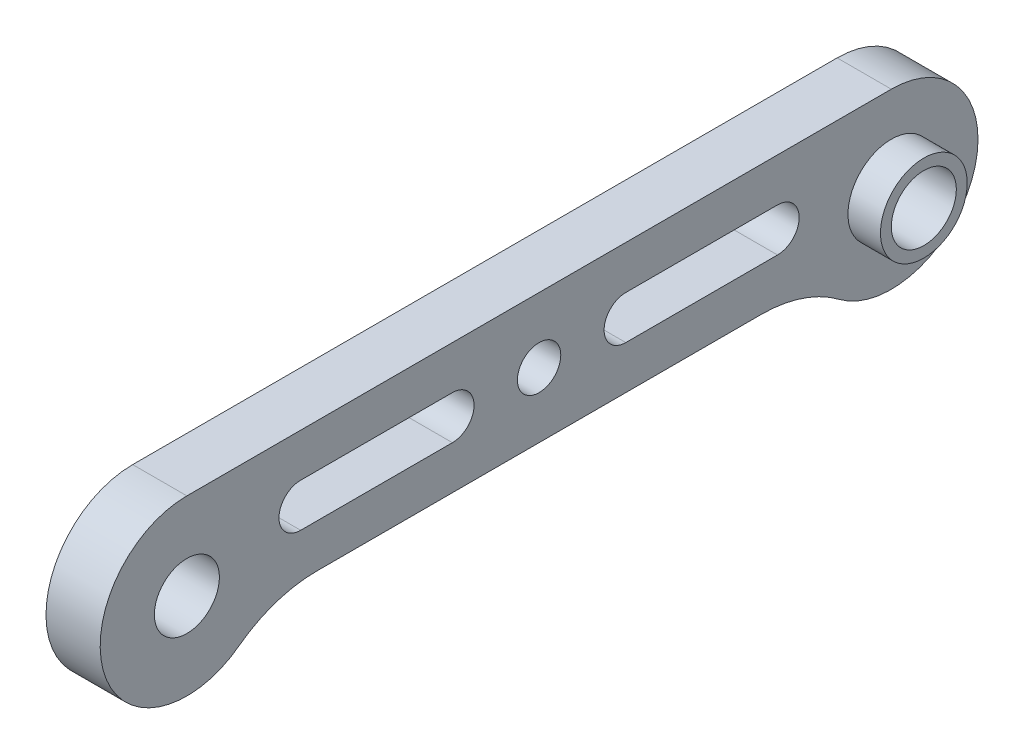
SolidWorks part; units mm, degrees
material "ABS"
ref_plane "前视基准面" through (0, 0, 0) normal (0, 0, 1) x (1, 0, 0)
ref_plane "上视基准面" through (0, 0, 0) normal (0, 1, 0) x (1, 0, 0)
ref_plane "右视基准面" through (0, 0, 0) normal (1, 0, 0) x (0, 0, -1)
other "Configuration Table"
sketch "草图1" plane through (0, 0, 0) normal (1, 0, 0) x (0, 0, -1)
  line L0 (0, 0) -> (-65, 0) construction
  line L1 (-65, 8) -> (0, 8)
  line L2 (-6.9282, -4) -> (-58.0718, -4)
  line L3 (0, -4) -> (-65, -4) construction
  circle A0 centre (-65, 0) radius 3
  circle A2 centre (-65, 0) radius 5 construction
  circle A3 centre (0, 0) radius 5 construction
  arc A4 (-65, 8) -> (-58.0718, -4) centre (-65, 0) ccw
  arc A5 (-6.9282, -4) -> (0, 8) centre (0, 0) ccw
  circle A6 centre (0, 0) radius 3
  dimension "D2" = 6
  dimension "D3" = 10
  dimension "D4" = 16
  dimension "D5" = 16
  dimension "D7" = 6
  dimension "D1" = 65
  dimension "D6" = 4
extrude "凸台-拉伸1" add sketch "草图1" along normal blind 5 contours L2 A5 L1 A4 A0 A6 region at (0, 1.3885, 32.5)
fillet "圆角1" radius 12 2 edges at (2.5, -4, 6.9282) (2.5, -4, 58.0718)
sketch "草图4" plane through (5, 0, 0) normal (1, 0, 0) x (0, 0, -1)
  line L0 (-57, 2) -> (-8, 2) construction
  line L2 (-65, 8) -> (0, 8) construction
  line L3 (-32.5, 2) -> (-32.5, 8) construction
  line L4 (-54.5, 2) -> (-40.5, 2) construction
  line L5 (-54.5, 4) -> (-40.5, 4)
  line L6 (-54.5, 0) -> (-40.5, 0)
  line L7 (-24.5, 2) -> (-10.5, 2) construction
  line L8 (-24.5, 4) -> (-10.5, 4)
  line L9 (-24.5, 0) -> (-10.5, 0)
  circle A2 centre (-32.5, 2) radius 2
  circle A3 centre (-65, 0) radius 3 construction
  arc A4 (-54.5, 4) -> (-54.5, 0) centre (-54.5, 2) ccw
  arc A5 (-40.5, 0) -> (-40.5, 4) centre (-40.5, 2) ccw
  arc A6 (-24.5, 4) -> (-24.5, 0) centre (-24.5, 2) ccw
  arc A7 (-10.5, 0) -> (-10.5, 4) centre (-10.5, 2) ccw
  point P11 (-47.5, 2)
  point P17 (-17.5, 2)
  dimension "D2" = 8
  dimension "D3" = 4
  dimension "D6" = 2
  dimension "D1" = 6
  dimension "D4" = 8
  dimension "D5" = 8
  dimension "D7" = 14
  dimension "D8" = 14
extrude "切除-拉伸1" cut sketch "草图4" against normal up to surface (5 mm away) up to face at (0, 0, -3)
sketch "草图5" plane through (0, 0, 0) normal (-1, 0, 0) x (0, 0, 1)
  circle A0 centre (0, 0) radius 4
  circle A1 centre (0, 0) radius 3
  circle A2 centre (0, 0) radius 3 construction
  circle A3 centre (65, 0) radius 3 construction
  circle A4 centre (65, 0) radius 4 construction
  circle A5 centre (65, 0) radius 3 construction
  dimension "D1" = 1
  dimension "D2" = 1
extrude "凸台-拉伸2" add sketch "草图5" along normal blind 3
extrude "凸台-拉伸3" add sketch "草图5<2>" against normal blind 3 from surface starting at face at (5, 2, 17.5)
sketch "草图5<2>" plane through (0, 0, 0) normal (-1, 0, 0) x (0, 0, 1) same geometry as "草图5"
